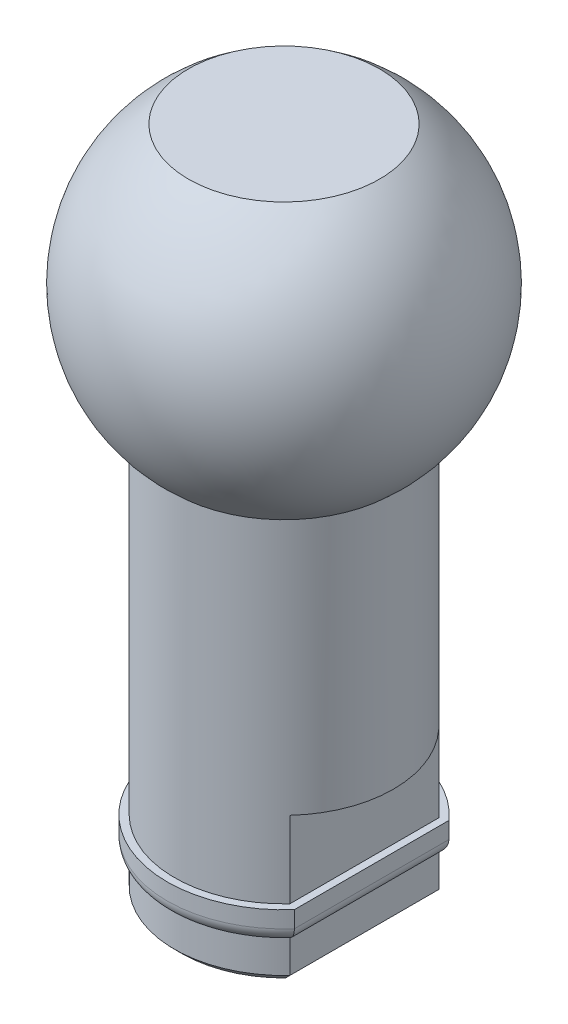
SolidWorks part; units mm, degrees
ref_plane "Front Plane" through (0, 0, 0) normal (0, 0, 1) x (1, 0, 0)
ref_plane "Top Plane" through (0, 0, 0) normal (0, 1, 0) x (1, 0, 0)
ref_plane "Right Plane" through (0, 0, 0) normal (1, 0, 0) x (0, 0, -1)
sketch "Sketch1" plane through (0, 0, 0) normal (0, 1, 0) x (1, 0, 0)
  circle A0 centre (0, 0) radius 7.5
extrude "Boss-Extrude1" add sketch "Sketch1" along normal blind 25
sketch "Sketch2" plane through (0, 0, 0) normal (1, 0, 0) x (0, 0, -1)
  line L1 (0, 47.5) -> (0, 45.7056) construction
  line L3 (7.5, 25) -> (-7.5, 25) construction
  line L12 (7.5, 25) -> (7.5, 27.5322)
  line L13 (7.5, 25) -> (0, 25)
  line L14 (0, 47.5) -> (0, 25) construction
  line L15 (0, 45.7056) -> (0, 25)
  line L16 (6.5454, 45.7056) -> (0, 45.7056)
  arc A5 (6.5454, 45.7056) -> (7.5, 27.5322) centre (0, 36.25) cw
revolve "Revolve1" add sketch "Sketch2" angle 360 about L15
sketch "Sketch3" plane through (0, 0, 0) normal (0, -1, 0) x (1, 0, 0)
  line L0 (7.5, 0) -> (5.5, 0) construction
  line L1 (5.5, 0) -> (5.5, 5.099)
  line L2 (5.5, 0) -> (5.5, -5.099)
  circle A0 centre (0, 0) radius 7.5 construction
  circle A1 centre (0, 0) radius 7.5 construction
  arc A2 (5.5, 5.099) -> (5.5, -5.099) centre (0, 0) cw
extrude "Cut-Extrude1" cut sketch "Sketch3" against normal blind 10 contours A2 L2 L1
ref_plane "SnapFeature-Plane" through (0, 3.75, 0) normal (0, 1, 0) x (1, 0, 0)
sketch "Sketch4" plane through (0, 3.75, 0) normal (0, 1, 0) x (1, 0, 0)
  line L0 (5.5, 0) -> (6, 0) construction
  line L1 (5.5, -5.099) -> (5.5, 5.099) construction
  line L4 (-7.5, 0) -> (-8, 0) construction
  line L5 (6, 5.2915) -> (6, -5.2915)
  arc A2 (5.5, 5.099) -> (5.5, -5.099) centre (0, 0) ccw construction
  arc A4 (6, 5.2915) -> (6, -5.2915) centre (0, 0) ccw
extrude "Boss-Extrude2" add sketch "Sketch4" along normal mid plane 2
fillet "Fillet1" radius 1 2 edges at (-8, 2.75, 0) (6, 2.75, 0)
chamfer "Chamfer3" distance 0.5 angle 45 2 edges at (5.5, 0, 0) (-7.5, 0, 0)
